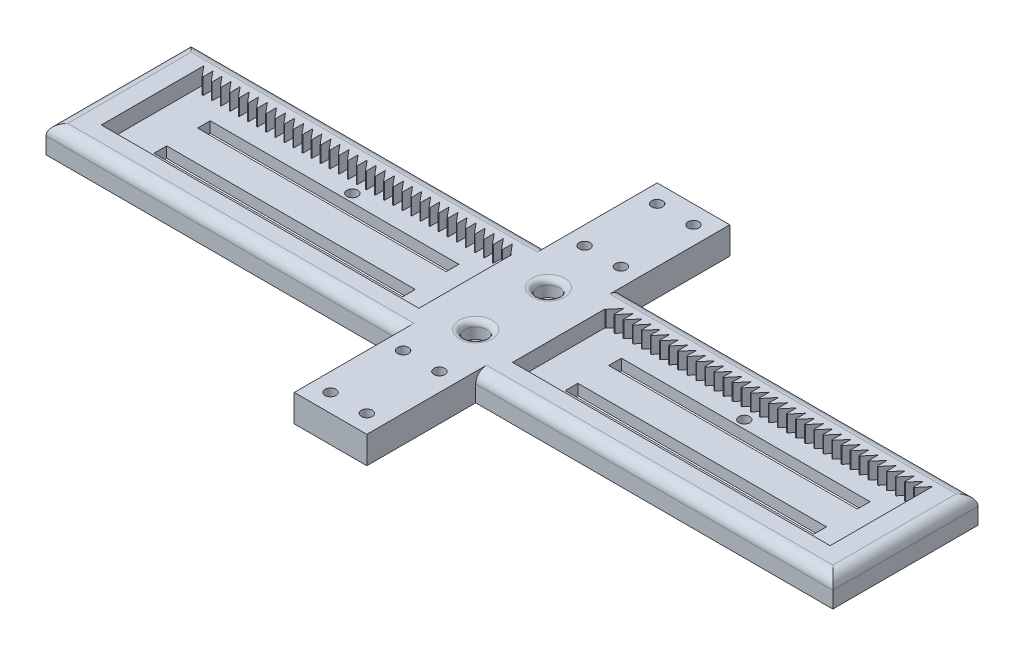
SolidWorks part; units mm, degrees
ref_plane "Front Plane" through (0, 0, 0) normal (0, 0, 1) x (1, 0, 0)
ref_plane "Top Plane" through (0, 0, 0) normal (0, 1, 0) x (1, 0, 0)
ref_plane "Right Plane" through (0, 0, 0) normal (1, 0, 0) x (0, 0, -1)
sketch "Sketch2" plane through (0, 0, 0) normal (0, 1, 0) x (1, 0, 0)
  line L0 (-12.9, 12.5) -> (-15.4, 15.5)
  line L2 (-108.4, 20) -> (-108.4, -20)
  line L5 (-100.4, 12.75) -> (-12.9, 12.75)
  line L6 (-100.4, 12.75) -> (-100.4, -12.75)
  line L7 (-100.4, -12.75) -> (-12.9, -12.75)
  line L8 (-12.9, 12.75) -> (-12.9, -12.75)
  line L9 (-108.4, 0) -> (-100.4, 0) construction
  line L10 (-15.4, 15.5) -> (-15.4, 12.5)
  line L11 (-15.4, 12.5) -> (-17.9, 15.5)
  line L12 (-17.9, 15.5) -> (-17.9, 12.5)
  line L13 (-17.9, 12.5) -> (-20.4, 15.5)
  line L14 (-20.4, 15.5) -> (-20.4, 12.5)
  line L15 (-20.4, 12.5) -> (-22.9, 15.5)
  line L16 (-22.9, 15.5) -> (-22.9, 12.5)
  line L17 (-22.9, 12.5) -> (-25.4, 15.5)
  line L18 (-25.4, 15.5) -> (-25.4, 12.5)
  line L19 (-25.4, 12.5) -> (-27.9, 15.5)
  line L20 (-27.9, 15.5) -> (-27.9, 12.5)
  line L21 (-27.9, 12.5) -> (-30.4, 15.5)
  line L22 (-30.4, 15.5) -> (-30.4, 12.5)
  line L23 (-30.4, 12.5) -> (-32.9, 15.5)
  line L24 (-32.9, 15.5) -> (-32.9, 12.5)
  line L25 (-32.9, 12.5) -> (-35.4, 15.5)
  line L26 (-35.4, 15.5) -> (-35.4, 12.5)
  line L27 (-35.4, 12.5) -> (-37.9, 15.5)
  line L28 (-37.9, 15.5) -> (-37.9, 12.5)
  line L29 (-37.9, 12.5) -> (-40.4, 15.5)
  line L30 (-40.4, 15.5) -> (-40.4, 12.5)
  line L31 (-40.4, 12.5) -> (-42.9, 15.5)
  line L32 (-42.9, 15.5) -> (-42.9, 12.5)
  line L33 (-42.9, 12.5) -> (-45.4, 15.5)
  line L34 (-45.4, 15.5) -> (-45.4, 12.5)
  line L35 (-45.4, 12.5) -> (-47.9, 15.5)
  line L36 (-47.9, 15.5) -> (-47.9, 12.5)
  line L37 (0, 0) -> (0, 9.3891) construction
  line L38 (0, -20) -> (0, 20)
  line L39 (-87.9, -12.75) -> (-87.9, -5.7094) construction
  line L41 (-25.4, 12.75) -> (-25.4, -12.75) construction
  line L45 (-65.4, 12.5) -> (-67.9, 15.5)
  line L46 (-47.9, 12.5) -> (-50.4, 15.5)
  line L47 (-50.4, 15.5) -> (-50.4, 12.5)
  line L48 (-50.4, 12.5) -> (-52.9, 15.5)
  line L49 (-52.9, 15.5) -> (-52.9, 12.5)
  line L50 (-52.9, 12.5) -> (-55.4, 15.5)
  line L51 (-55.4, 15.5) -> (-55.4, 12.5)
  line L52 (-55.4, 12.5) -> (-57.9, 15.5)
  line L53 (-57.9, 15.5) -> (-57.9, 12.5)
  line L54 (-57.9, 12.5) -> (-60.4, 15.5)
  line L55 (-60.4, 15.5) -> (-60.4, 12.5)
  line L56 (-60.4, 12.5) -> (-62.9, 15.5)
  line L57 (-62.9, 15.5) -> (-62.9, 12.5)
  line L58 (-62.9, 12.5) -> (-65.4, 15.5)
  line L59 (-65.4, 15.5) -> (-65.4, 12.5)
  line L60 (-108.4, 20) -> (0, 20)
  line L61 (-108.4, -20) -> (0, -20)
  line L62 (-67.9, 15.5) -> (-67.9, 12.5)
  line L63 (-67.9, 12.5) -> (-70.4, 15.5)
  line L64 (-70.4, 15.5) -> (-70.4, 12.5)
  line L65 (-70.4, 12.5) -> (-72.9, 15.5)
  line L66 (-72.9, 15.5) -> (-72.9, 12.5)
  line L67 (-72.9, 12.5) -> (-75.4, 15.5)
  line L68 (-75.4, 15.5) -> (-75.4, 12.5)
  line L69 (-75.4, 12.5) -> (-77.9, 15.5)
  line L70 (-77.9, 15.5) -> (-77.9, 12.5)
  line L71 (-77.9, 12.5) -> (-80.4, 15.5)
  line L72 (-80.4, 15.5) -> (-80.4, 12.5)
  line L73 (-80.4, 12.5) -> (-82.9, 15.5)
  line L74 (0, 20) -> (0, -20) construction
  line L75 (-82.9, 15.5) -> (-82.9, 12.5)
  line L76 (-82.9, 12.5) -> (-85.4, 15.5)
  line L77 (-85.4, 15.5) -> (-85.4, 12.5)
  line L78 (-85.4, 12.5) -> (-87.9, 15.5)
  line L79 (-87.9, 15.5) -> (-87.9, 12.5)
  line L80 (-87.9, 12.5) -> (-90.4, 15.5)
  line L81 (-90.4, 15.5) -> (-90.4, 12.5)
  line L82 (-90.4, 12.5) -> (-92.9, 15.5)
  line L83 (-92.9, 15.5) -> (-92.9, 12.5)
  line L84 (-92.9, 12.5) -> (-95.4, 15.5)
  line L85 (-95.4, 15.5) -> (-95.4, 12.5)
  line L86 (-95.4, 12.5) -> (-97.9, 15.5)
  line L87 (-97.9, 15.5) -> (-97.9, 12.5)
  line L88 (-97.9, 12.5) -> (-100.4, 15.5)
  line L89 (-100.4, 15.5) -> (-100.4, 12.5)
  point P5 (-108.4, 0)
  dimension "D2" = 40
  dimension "D3" = 12.5
  dimension "D4" = 25.4
  dimension "D5" = 12.5
  dimension "D6" = 2.5
  dimension "D7" = 3
  dimension "D8" = 25.5
  dimension "D9" = 12.5
  dimension "D10" = 8
  dimension "D11" = 87.9
  dimension "D15" = 35
extrude "Boss-Extrude1" add sketch "Sketch2" against normal blind 3 contours L2 L61 L38 L60
extrude "Boss-Extrude2" add sketch "Sketch2<3>" along normal blind 4.5 contours L2 L8 L7 L6 L5 region at (-54.2, 0, -18.8446)
sketch "Sketch2<3>" plane through (0, 0, 0) normal (0, 1, 0) x (1, 0, 0) same geometry as "Sketch2"
sketch "Sketch3" plane through (0, 0, 0) normal (0, 1, 0) x (1, 0, 0)
  line L0 (-100.4, 15.5) -> (-100.4, -12.75) construction
  line L1 (-100.4, 7.75) -> (50.52, 7.75)
  line L2 (-100.4, 7.75) -> (-100.4, 4.25)
  line L3 (-100.4, 4.25) -> (50.52, 4.25)
  line L4 (50.52, 7.75) -> (50.52, 4.25)
  line L6 (-100.4, 0) -> (-44.0832, 0) construction
  line L7 (-90.9, 4.25) -> (-90.9, 7.75)
  line L8 (-22.4, 4.25) -> (-22.4, 7.75)
  line L9 (-12.9, 12.75) -> (-12.9, -12.75) construction
  line L10 (-24.94, 4.25) -> (-24.94, -3.7317) construction
  line L11 (-22.4, -4.25) -> (-22.4, -7.75)
  line L12 (-90.9, -4.25) -> (-90.9, -7.75)
  line L13 (-100.4, -4.25) -> (50.52, -4.25)
  line L14 (50.52, -7.75) -> (50.52, -4.25)
  line L15 (-100.4, -7.75) -> (50.52, -7.75)
  line L16 (-100.4, -7.75) -> (-100.4, -4.25)
  line L18 (41.02, -4.25) -> (41.02, -7.75)
  line L19 (41.02, 4.25) -> (41.02, 7.75)
  line L21 (-100.4, 15.5) -> (-100.4, -12.75) construction
  line L22 (-100.4, 15.5) -> (-100.4, -12.75)
  point P10 (-100.4, 6)
  dimension "D1" = 3.5
  dimension "D2" = 6
  dimension "D3" = 9.5
  dimension "D4" = 9.5
extrude "Cut-Extrude1" cut sketch "Sketch3" against normal through all contours L3 L8 L1 L7 | L12 L15 L11 L13 region at (-56.65, 0, -6) region at (-56.65, 0, 6)
sketch "Sketch4" plane through (0, 4.5, 0) normal (0, 1, 0) x (1, 0, 0)
  line L2 (0, 10) -> (0, 0) construction
  circle A0 centre (0, 10) radius 1.75
  circle A2 centre (54, 10) radius 1.75
  circle A3 centre (54, -10) radius 1.75
  circle A4 centre (0, -10) radius 1.75
  dimension "D1" = 3.5
  dimension "D2" = 2
  dimension "D3" = 10
  dimension "D4" = 2
  dimension "D5" = 10
extrude "Cut-Extrude3" cut sketch "Sketch4" against normal through all contours A0 | A4 | A3 | A2 region at (0, 4.5, -10) region at (54, 4.5, -10) region at (54, 4.5, 10) region at (0, 4.5, 10)
sketch "Sketch5" plane through (0, 4.5, 0) normal (0, 1, 0) x (1, 0, 0)
  circle A1 centre (0, 10) radius 3
  circle A4 centre (0, -10) radius 3
extrude "Cut-Extrude4" cut sketch "Sketch5" against normal offset from surface (4.5 mm away) 3 up to face at (-56.65, -3, -6)
sketch "Sketch7" plane through (0, -3, 0) normal (0, -1, 0) x (1, 0, 0)
  circle A0 centre (-54, 10) radius 1.5
  circle A1 centre (-54, -10) radius 1.5
  arc A2 (0, -8.25) -> (0, -11.75) centre (0, -10) ccw construction
  arc A3 (0, 11.75) -> (0, 8.25) centre (0, 10) ccw construction
  arc A4 (0, -8.25) -> (0, -11.75) centre (0, -10) ccw
  arc A5 (0, 11.75) -> (0, 8.25) centre (0, 10) ccw
  dimension "D1" = 3
  dimension "D2" = 3
  dimension "D3" = 54
extrude "Cut-Extrude5" cut sketch "Sketch7" against normal blind 3 contours A0 | A1
sketch "Sketch9" plane through (0, 4.5, 0) normal (0, 1, 0) x (1, 0, 0)
  line L1 (0, 20) -> (-10, 20)
  line L2 (0, 20) -> (0, 50)
  line L3 (0, 50) -> (-10, 50)
  line L4 (-10, 20) -> (-10, 50)
  line L5 (0, -20) -> (-10, -20)
  line L6 (0, -20) -> (0, -50)
  line L7 (0, -50) -> (-10, -50)
  line L8 (-10, -20) -> (-10, -50)
  dimension "D1" = 30
  dimension "D2" = 30
  dimension "D3" = 10
  dimension "D4" = 10
extrude "Boss-Extrude3" add sketch "Sketch9" against normal up to surface (7.5 mm away) up to face at (-54, -3, 8.5)
sketch "Sketch10" plane through (0, 4.5, 0) normal (0, 1, 0) x (1, 0, 0)
  line L0 (0, 13) -> (0, 50) construction
  line L1 (0, 0) -> (-6.4734, 0) construction
  line L2 (0, -7) -> (0, 7) construction
  circle A0 centre (-5, 45) radius 1.5
  circle A1 centre (-5, 25) radius 1.5
  circle A2 centre (-5, -45) radius 1.5
  circle A3 centre (-5, -25) radius 1.5
  dimension "D1" = 3
  dimension "D3" = 3
  dimension "D2" = 5
  dimension "D4" = 5
  dimension "D5" = 20
  dimension "D6" = 25
extrude "Cut-Extrude6" cut sketch "Sketch10" against normal blind 6 contours A1 | A3 | A2 | A0 region at (-5, 4.5, -25) region at (-5, 4.5, 45) region at (-5, 4.5, 25)
mirror "Mirror1" about plane through (0, 0, 0) normal (1, 0, 0) of bodies 110 106
fillet "Fillet2" radius 3 6 edges at (108.4, 4.5, 0) (59.2, 4.5, -20) (59.2, 4.5, 20) (-108.4, 4.5, 0) (-59.2, 4.5, 20) (-59.2, 4.5, -20)
fillet "Fillet3" radius 1.5 2 edges at (0, 4.5, 13) (0, 4.5, -7)
